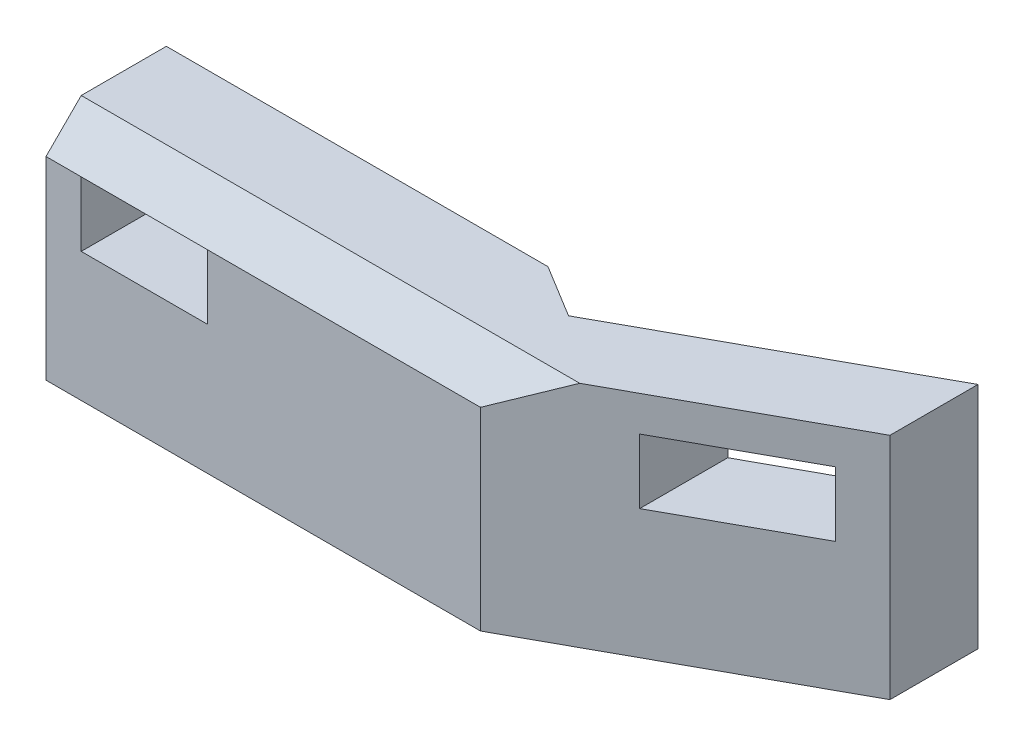
SolidWorks part; units mm, degrees
ref_plane "Front Plane" through (0, 0, 0) normal (0, 0, 1) x (1, 0, 0)
ref_plane "Top Plane" through (0, 0, 0) normal (0, 1, 0) x (1, 0, 0)
ref_plane "Right Plane" through (0, 0, 0) normal (1, 0, 0) x (0, 0, -1)
sketch "Sketch1" plane through (0, 0, 0) normal (0, 1, 0) x (1, 0, 0)
  line L0 (6.5, -2.05) -> (8.3, -2.05)
  line L1 (-6.5, -2.05) -> (6.5, -2.05)
  line L2 (-6.5, -2.05) -> (-6.5, 2.05)
  line L3 (-6.5, 2.05) -> (6.5, 2.05)
  line L4 (6.5, -2.05) -> (6.5, 2.05)
  line L5 (-6.5, -2.05) -> (6.5, 2.05) construction
  line L6 (-6.5, 2.05) -> (6.5, -2.05) construction
  line L7 (8.3, -2.05) -> (17.3, 2.8991)
  line L8 (17.3, 2.8991) -> (17.3, 5.8991)
  line L9 (6.5, 2.05) -> (13.4996, 5.8991)
  line L10 (13.4996, 5.8991) -> (17.3, 5.8991)
  point P0 (0, 0)
  dimension "D1" = 13
  dimension "D2" = 4.1
  dimension "D3" = 1.8
  dimension "D4" = 9
  dimension "D5" = 4.9491
  dimension "D6" = 3
extrude "Boss-Extrude1" add sketch "Sketch1" along normal mid plane 7.8 contours L10 L9 L4 L0 L7 L8 | L1 L4 L3 L2 region at (11.6578, 0, -2.2342) region at (0, 0, 0)
sketch "Sketch2" plane through (0, -3.9, 0) normal (0, -1, 0) x (1, 0, 0)
  line L0 (17.3, -5.8991) -> (8.3, -0.95)
  line L1 (8.3, -0.95) -> (6.5, -2.05)
  line L2 (8.3, 2.05) -> (17.3, -2.8991) construction
  line L3 (6.5, -2.05) -> (13.4996, -5.8991)
  line L4 (13.4996, -5.8991) -> (17.3, -5.8991)
  dimension "D1" = 0
extrude "Cut-Extrude1" cut sketch "Sketch2" against normal offset from surface (6.6 mm away) 1.2 up to face at (7.1285, 3.9, -2.0996)
sketch "Sketch3" plane through (0, 0, 2.05) normal (0, 0, 1) x (1, 0, 0)
  line L0 (-6.5, 3.9) -> (-6.5, -3.9) construction
  line L1 (-5.3, -0.5) -> (-1, -0.5)
  line L2 (-5.3, -0.5) -> (-5.3, -2.7)
  line L3 (-5.3, -2.7) -> (-1, -2.7)
  line L4 (-1, -0.5) -> (-1, -2.7)
  line L5 (-5.3, -0.5) -> (-1, -2.7) construction
  line L6 (-5.3, -2.7) -> (-1, -0.5) construction
  line L7 (-6.5, -3.9) -> (8.3, -3.9) construction
  line L8 (17.3, 3.9) -> (17.3, -3.9) construction
  line L9 (11.8, -0.5) -> (16.1, -0.5)
  line L10 (11.8, -0.5) -> (11.8, -2.7)
  line L11 (11.8, -2.7) -> (16.1, -2.7)
  line L12 (16.1, -0.5) -> (16.1, -2.7)
  line L13 (11.8, -0.5) -> (16.1, -2.7) construction
  line L14 (11.8, -2.7) -> (16.1, -0.5) construction
  line L15 (8.3, -3.9) -> (17.3, -3.9) construction
  point P0 (-3.15, -1.6)
  point P9 (13.95, -1.6)
  dimension "D1" = 2.2
  dimension "D2" = 4.3
  dimension "D3" = 1.2
  dimension "D4" = 1.2
  dimension "D5" = 4.3
  dimension "D6" = 2.2
  dimension "D7" = 1.2
  dimension "D8" = 1.2
extrude "Cut-Extrude2" cut sketch "Sketch3" against normal through all both and the other way through all
chamfer "Chamfer1" distance 1.2 angle 45 1 edges at (0.9, -3.9, 2.05)
mirror "Mirror1" about plane through (0, 3.9, 0) normal (0, 1, 0) of bodies 103
delete or keep bodies "-1" type delete bodies bodies 103
